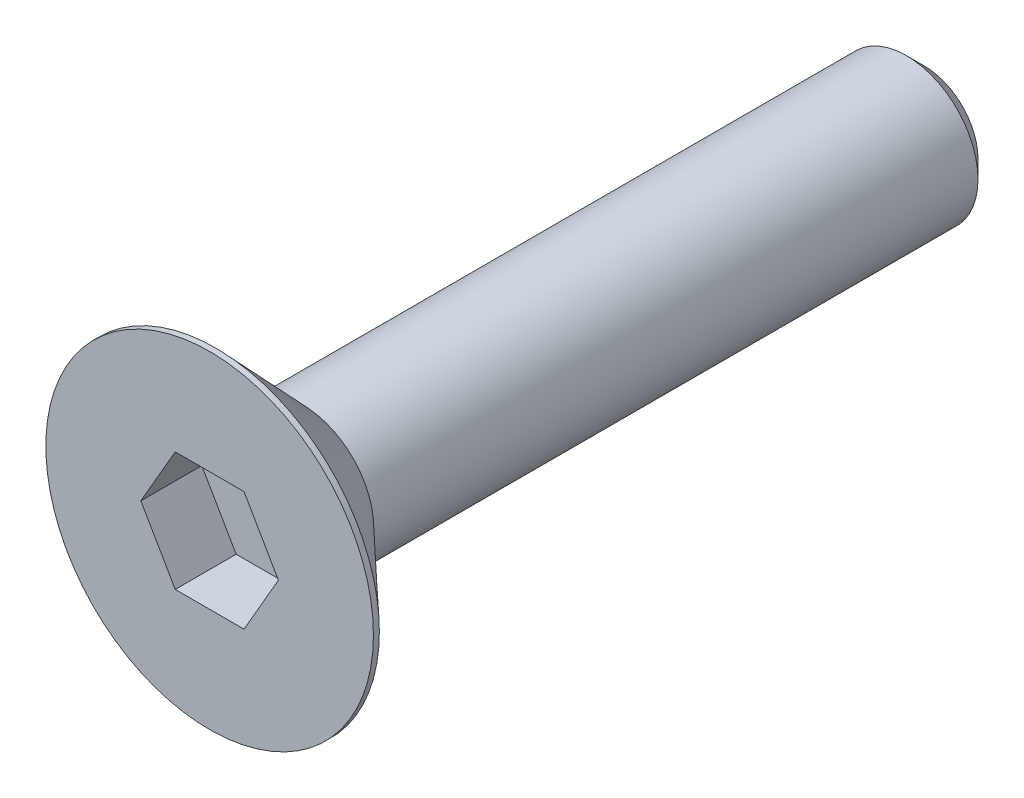
SolidWorks part; units mm, degrees
ref_plane "Front Plane" through (0, 0, 0) normal (0, 0, 1) x (1, 0, 0)
ref_plane "Top Plane" through (0, 0, 0) normal (0, 1, 0) x (1, 0, 0)
ref_plane "Right Plane" through (0, 0, 0) normal (1, 0, 0) x (0, 0, -1)
sketch "Screw Section" plane through (0, 0, 0) normal (0, 1, 0) x (1, 0, 0)
  line L0 (0, 12) -> (1.2, 12)
  line L1 (1.2, 12) -> (1.2, 1.65)
  line L2 (1.2, 1.65) -> (2.75, 1.65)
  line L3 (2.75, 1.65) -> (2.75, 0)
  line L4 (2.75, 0) -> (0, 0)
  line L5 (0, 0) -> (0, 12)
  line L6 (0, -10.123) -> (0, 10.123) construction
  dimension "D1" = 1.2
  dimension "D2" = 2.75
  dimension "D3" = 12
  dimension "D4" = 1.65
  dimension "D5" = 10.123
  dimension "D6" = 10.123
revolve "Screw Blank Revolve" add sketch "Screw Section" angle 360 about L6
chamfer "Shank Tip Chamfer" distance 0.3 1 edges at (1.2, 0, -12) tangent propagation no
chamfer "Countersunk Head Chamfer" distance 1.65 distance2 1.55 1 edges at (2.75, 0, -1.65) tangent propagation no first distance on face at (1.2, 0, -1.65)
sketch "Hex Drive Sketch" plane through (0, 0, 0) normal (0, 0, 1) x (1, 0, 0)
  line L1 (1.1547, 0) -> (0.5774, 1)
  line L2 (0.5774, 1) -> (-0.5774, 1)
  line L3 (-0.5774, 1) -> (-1.1547, 0)
  line L4 (-1.1547, 0) -> (-0.5774, -1)
  line L5 (-0.5774, -1) -> (0.5774, -1)
  line L6 (0.5774, -1) -> (1.1547, 0)
  circle A0 centre (0, 0) radius 1 construction
  dimension "D1" = 2
extrude "Hex Drive Cut" cut sketch "Hex Drive Sketch" against normal blind 1.023
equation "\"nominal_length\"= 12.0mm 'Screw length: under pan head or including flat head"
equation "\"model_shank_radius\"= 1.2mm 'Clearance envelope minor shank radius; thread is not modeled"
equation "\"head_diameter\"= 5.5mm 'Head outside diameter"
equation "\"head_height\"= 1.65mm 'Head axial height"
equation "\"drive_across_flats\"= 2mm 'Hex drive across flats"
equation "\"tip_chamfer\"= 0.3mm 'Shank tip chamfer"
equation "\"drive_depth\"= 1.023mm 'Hex socket depth"
equation "\"axis_reference_halfspan\"= 10.123mm 'Half display length of the construction axis; avoids sharing a profile endpoint"
equation "\"D1@Screw Section\"= \"model_shank_radius\""
equation "\"D2@Screw Section\"= \"head_diameter\" / 2"
equation "\"D3@Screw Section\"= \"nominal_length\""
equation "\"D4@Screw Section\"= \"head_height\""
equation "\"D5@Screw Section\"= \"axis_reference_halfspan\""
equation "\"D6@Screw Section\"= \"axis_reference_halfspan\""
equation "\"full_turn\"= 360deg 'Full circular extent for revolves and patterns"
equation "\"D1@Screw Blank Revolve\"= \"full_turn\""
equation "\"D1@Shank Tip Chamfer\"= \"tip_chamfer\""
equation "\"D1@Countersunk Head Chamfer\"= \"head_height\""
equation "\"D3@Countersunk Head Chamfer\"= \"head_diameter\" / 2 - \"model_shank_radius\""
equation "\"D1@Hex Drive Sketch\"= \"drive_across_flats\""
equation "\"D1@Hex Drive Cut\"= \"drive_depth\""
